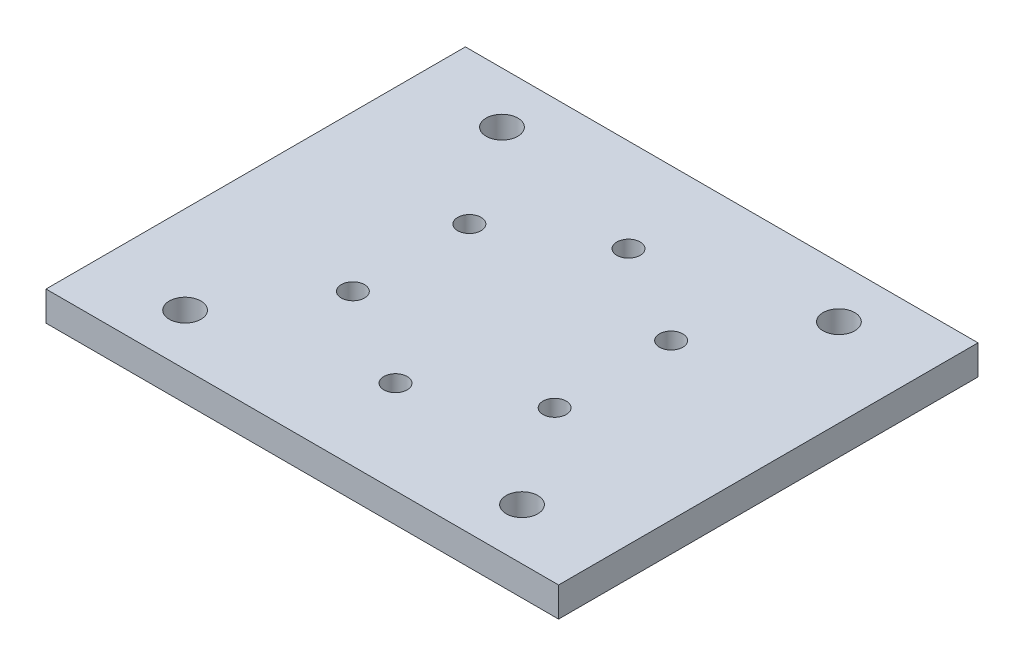
SolidWorks part; units mm, degrees
ref_plane "Front Plane" through (0, 0, 0) normal (0, 0, 1) x (1, 0, 0)
ref_plane "Top Plane" through (0, 0, 0) normal (0, 1, 0) x (1, 0, 0)
ref_plane "Right Plane" through (0, 0, 0) normal (1, 0, 0) x (0, 0, -1)
sketch "Sketch2" plane through (0, 0, 0) normal (0, 1, 0) x (1, 0, 0)
  line L0 (0, 0) -> (0, 90)
  line L1 (0, 90) -> (110, 90)
  line L2 (110, 90) -> (110, 0)
  line L3 (110, 0) -> (0, 0)
  dimension "D1" = 110
  dimension "D2" = 90
extrude "Boss-Extrude1" add sketch "Sketch2" along normal blind 6.35
sketch "Sketch3" plane through (0, 6.35, 0) normal (0, 1, 0) x (1, 0, 0)
  line L1 (110, 90) -> (0, 90) construction
  line L2 (0, 0) -> (110, 0) construction
  line L4 (55, 90) -> (55, 0) construction
  line L5 (0, 45) -> (55, 45) construction
  line L6 (55, 45) -> (110, 45) construction
  line L7 (0, 90) -> (0, 0) construction
  circle A0 centre (18.85, 79) radius 3.4
  circle A1 centre (18.85, 11) radius 3.4
  circle A2 centre (91.15, 11) radius 3.4
  circle A3 centre (91.15, 79) radius 3.4
  dimension "D4" = 6.8
  dimension "D3" = 11
  dimension "D2" = 18.85
extrude "Mounting Holes" cut sketch "Sketch3" against normal through all
sketch "Sketch4" plane through (0, 6.35, 0) normal (0, 1, 0) x (1, 0, 0)
  line L0 (18.85, 79) -> (91.15, 11) construction
  circle A0 centre (55, 45) radius 25 construction
  circle A1 centre (55, 70) radius 2.5
  circle A2 centre (76.6506, 57.5) radius 2.5
  circle A3 centre (76.6506, 32.5) radius 2.5
  circle A4 centre (55, 20) radius 2.5
  circle A5 centre (33.3494, 32.5) radius 2.5
  circle A6 centre (33.3494, 57.5) radius 2.5
  point P20 (55, 45)
  dimension "D1" = 50
  dimension "D2" = 5
  dimension "D3" = 6
extrude "Cut-Extrude1" cut sketch "Sketch4" against normal through all
sketch "Sketch5" plane through (0, 6.35, 0) normal (0, 1, 0) x (1, 0, 0)
  circle A0 centre (55, 45) radius 25 construction
  circle A1 centre (55, 20) radius 2.5 construction
  circle A2 centre (55, 20) radius 2.5 construction
  circle A3 centre (33.3494, 32.5) radius 2.5 construction
  circle A4 centre (33.3494, 32.5) radius 2.5 construction
  circle A5 centre (33.3494, 57.5) radius 2.5 construction
  circle A6 centre (33.3494, 57.5) radius 2.5 construction
  point P6 (0, 0)
equation "\"L1L\"=500"
equation "\"L1Thick\"=6.35"
equation "\"Harm-Drive-Outer\"=74.5"
equation "\"L1-Spacing\"=100"
equation "\"L-Bracket-HoleToWall\"=12.5"
equation "\"D3@Sketch3\"=\"L-Bracket-HoleToSide\""
equation "\"L-Bracket-HoleToSide\"=11"
equation "\"Bracket-Hole-D\"=6.8"
equation "\"D4@Sketch3\"=\"Bracket-Hole-D\""
equation "\"L1-Spacing\"=115.65"
equation "\"D2@Sketch3\"=\"L-Bracket-HoleToWall\"+\"L1Thick\""
